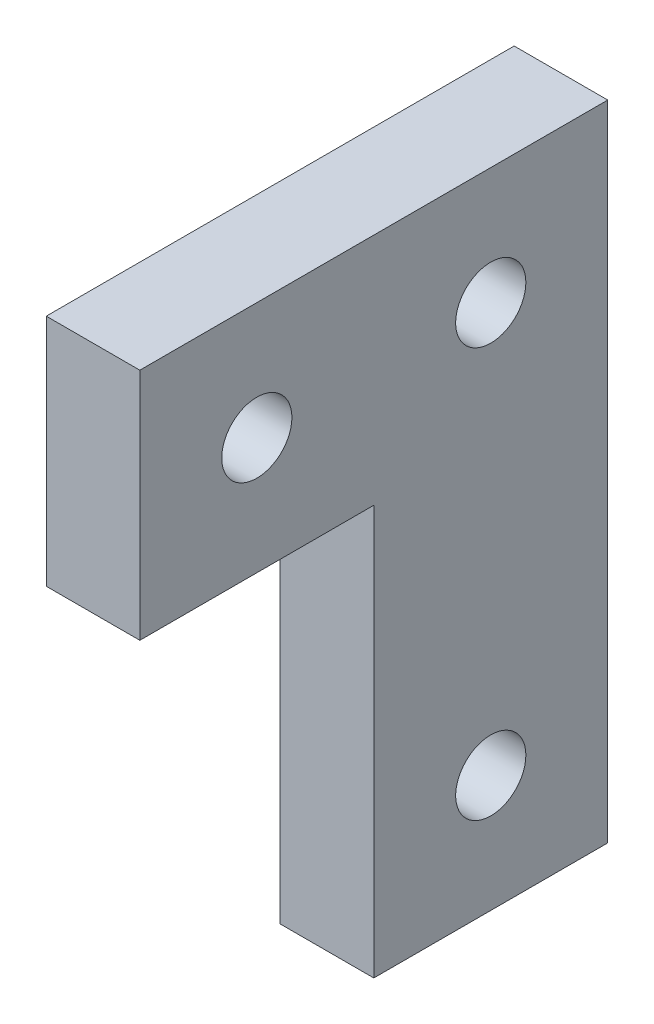
SolidWorks part; units mm, degrees
ref_plane "前视基准面" through (0, 0, 0) normal (0, 0, 1) x (1, 0, 0)
ref_plane "上视基准面" through (0, 0, 0) normal (0, 1, 0) x (1, 0, 0)
ref_plane "右视基准面" through (0, 0, 0) normal (1, 0, 0) x (0, 0, -1)
other "Configuration Table"
sketch "草图1" plane through (0, 0, 0) normal (1, 0, 0) x (0, 0, -1)
  line L0 (-6, -2) -> (-2, -2)
  line L1 (-6, 2) -> (2, 2)
  line L2 (-6, 2) -> (-6, -9)
  line L3 (-6, -9) -> (2, -9)
  line L4 (2, 2) -> (2, -9)
  line L5 (-2, -9) -> (-2, -2)
  circle A0 centre (0, 0) radius 0.6
  circle A1 centre (-4, 0) radius 0.6
  circle A2 centre (0, -7) radius 0.6
  dimension "D1" = 1.2
  dimension "D10" = 1.2
  dimension "D2" = 2
  dimension "D3" = 6
  dimension "D4" = 9
  dimension "D5" = 2
  dimension "D6" = 2
  dimension "D7" = 2
  dimension "D8" = 2
  dimension "D9" = 2
extrude "凸台-拉伸1" add sketch "草图1" along normal blind 1.6 contours L5 L3 L4 L1 L2 L0 A2 A1 A0 region at (0, -2.5807, 1.0507)
